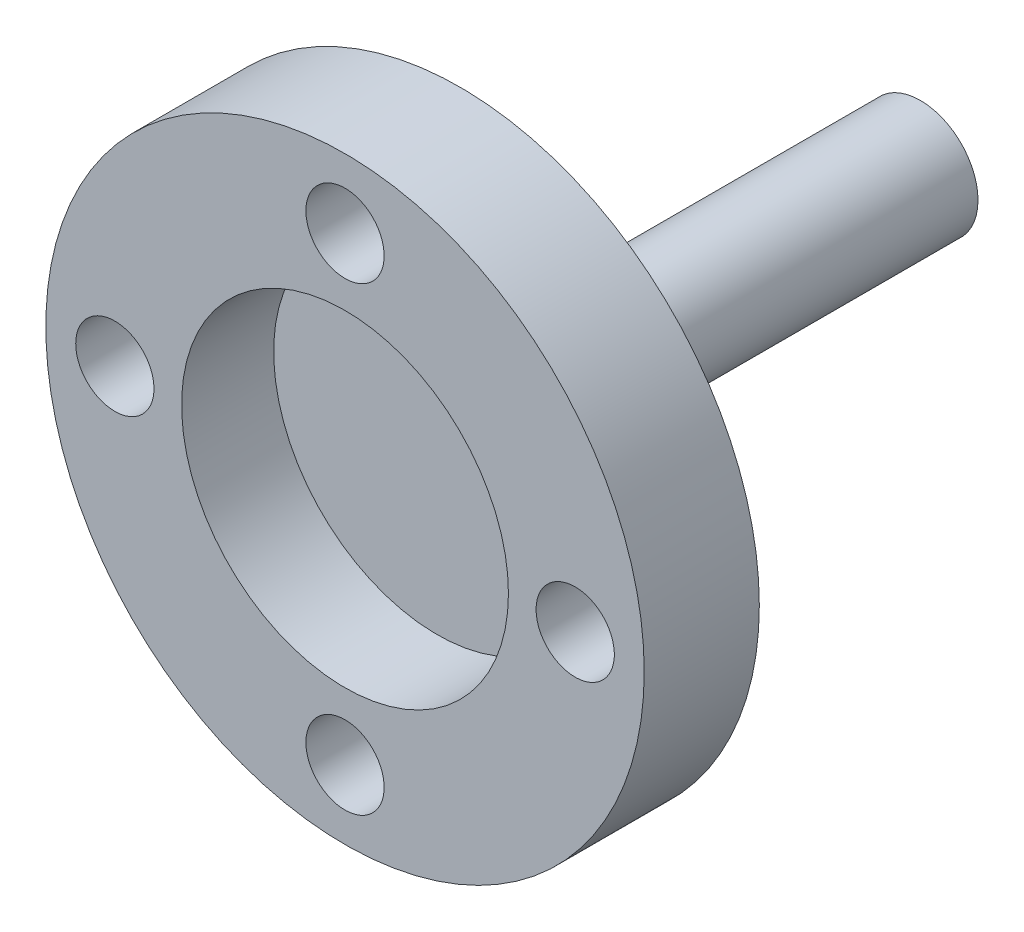
SolidWorks part; units mm, degrees
ref_plane "Спереди" through (0, 0, 0) normal (0, 0, 1) x (1, 0, 0)
ref_plane "Сверху" through (0, 0, 0) normal (0, 1, 0) x (1, 0, 0)
ref_plane "Справа" through (0, 0, 0) normal (1, 0, 0) x (0, 0, -1)
sketch "Эскиз1" plane through (0, 0, 0) normal (0, 0, 1) x (1, 0, 0)
  circle A0 centre (0, 0) radius 13
  dimension "D1" = 26
extrude "Бобышка-Вытянуть1" add sketch "Эскиз1" along normal blind 5
sketch "Эскиз2" plane through (0, 0, 5) normal (0, 0, 1) x (1, 0, 0)
  circle A0 centre (0, 0) radius 7.1
  dimension "D1" = 14.2
extrude "Вырез-Вытянуть1" cut sketch "Эскиз2" against normal blind 4
sketch "Эскиз3" plane through (0, 0, 0) normal (0, 0, -1) x (-1, 0, 0)
  circle A0 centre (0, 0) radius 2.5
  dimension "D1" = 5
extrude "Бобышка-Вытянуть2" add sketch "Эскиз3" along normal blind 20
sketch "Эскиз4" plane through (0, 0, 0) normal (0, 0, -1) x (-1, 0, 0)
  line L0 (0, 13) -> (0, -13) construction
  line L1 (13, 0) -> (-13, 0) construction
  circle A0 centre (0, 0) radius 10 construction
  circle A1 centre (0, 0) radius 13 construction
  dimension "D1" = 20
hole_wizard "Отверстие с зазором M31" positions "Эскиз6" profile "Эскиз5" hole size "M3" standard "Ansi Metric" end condition through all
sketch "Эскиз6" plane through (0, 0, 0) normal (0, 0, -1) x (-1, 0, 0)
  line L0 (0, 13) -> (0, -13) construction
  line L1 (13, 0) -> (-13, 0) construction
  circle A0 centre (0, 0) radius 10 construction
  point P0 (0, 10)
  point P6 (-10, 0)
  point P10 (0, -10)
  point P12 (10, 0)
sketch "Эскиз5" plane through (0, 10, 0) normal (1, 0, 0) x (0, 1, 0)
  line L0 (0, 0) -> (0, 5)
  line L1 (0, 5) -> (1.7, 5)
  line L2 (1.7, 5) -> (1.7, 0)
  line L5 (1.7, 0) -> (0, 0)
  line L11 (0, -6.35) -> (0, 107.95) construction
  dimension "Диаметр сквозного отверстия" = 3.4
  dimension "Глубина сквозного отверстия" = 5
